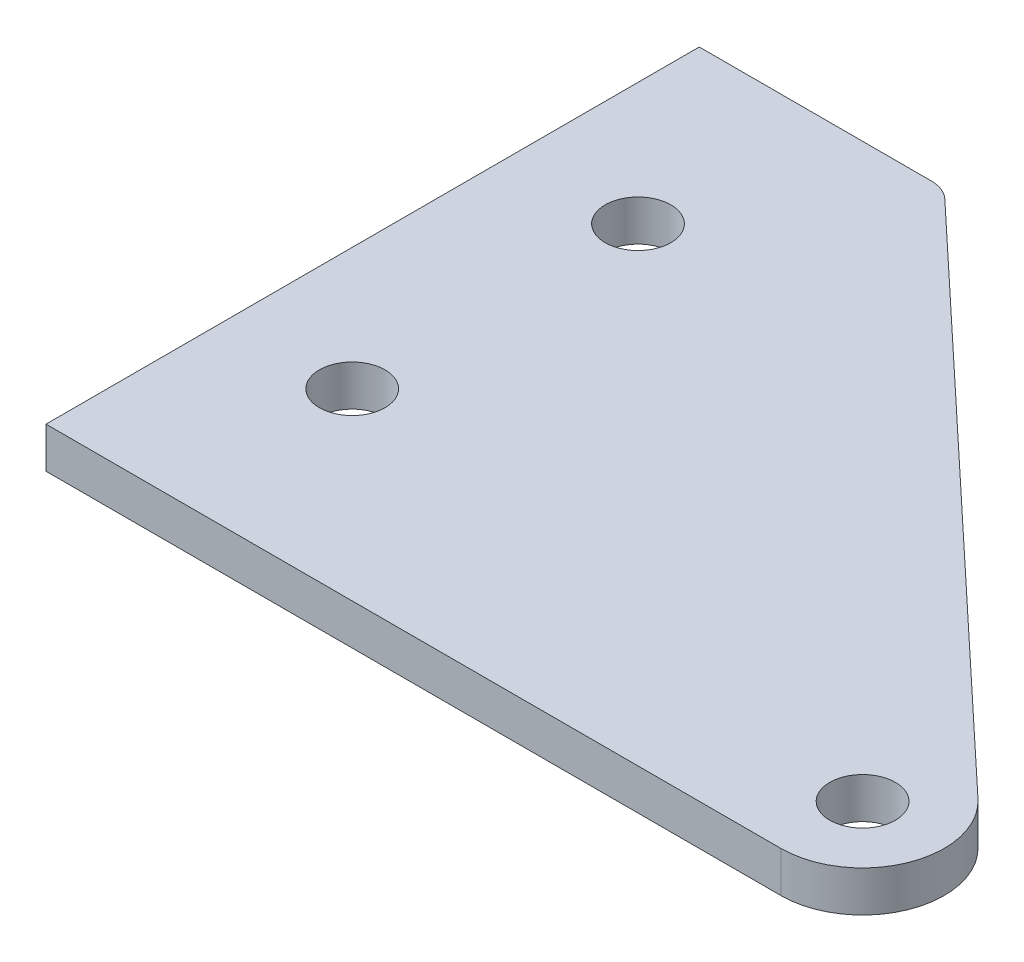
SolidWorks part; units mm, degrees
material "6061-T6 (SS)"
ref_plane "Front" through (0, 0, 0) normal (0, 0, 1) x (1, 0, 0)
ref_plane "Top" through (0, 0, 0) normal (0, 1, 0) x (1, 0, 0)
ref_plane "Right" through (0, 0, 0) normal (1, 0, 0) x (0, 0, -1)
sketch "Sketch1" plane through (0, 0, 0) normal (0, 1, 0) x (1, 0, 0)
  line L0 (0, 0) -> (0, 50.8)
  line L1 (0, 50.8) -> (19.05, 50.8)
  line L2 (0, 0) -> (57.15, 0)
  line L3 (19.05, 50.8) -> (61.4946, 10.9811)
  arc A0 (61.4946, 10.9811) -> (57.15, 0) centre (57.15, 6.35) cw
  dimension "D1" = 50.8
  dimension "D2" = 57.15
  dimension "D3" = 6.35
  dimension "D4" = 19.05
extrude "Boss-Extrude1" add sketch "Sketch1" along normal blind 3.175
hole_wizard "1/4-20 Tapped Hole1" positions "Sketch4" profile "Sketch3" tap size "1/4-20" standard "ANSI Inch" end condition through all
sketch "Sketch4" plane through (0, 0, 0) normal (0, -1, 0) x (-1, 0, 0)
  point P0 (-57.15, 6.35)
sketch "Sketch3" plane through (57.15, 0, -6.35) normal (1, 0, 0) x (0, 0, -1)
  line L0 (0, 0) -> (0, 3.175)
  line L1 (0, 3.175) -> (2.5527, 3.175)
  line L2 (2.5527, 3.175) -> (2.5527, 0)
  line L5 (2.5527, 0) -> (0, 0)
  line L11 (0, -6.35) -> (0, 107.95) construction
  dimension "Thru Tap Drill Dia." = 5.1054
  dimension "Thru Tap Drill Depth" = 3.175
cosmetic thread "Hole Thread1" parameters "D2"=6.35
hole_wizard "1/4-20 Tapped Hole2" positions "Sketch7" profile "Sketch8" tap size "1/4-20" standard "ANSI Inch" end condition through all
sketch "Sketch7" plane through (0, 3.175, 0) normal (0, 1, 0) x (1, 0, 0)
  line L4 (0, 0) -> (57.15, 0) construction
  line L7 (9.525, 50.8) -> (9.525, 0)
  line L8 (19.05, 50.8) -> (0, 50.8) construction
  point P0 (9.525, 36.5125)
  point P2 (9.525, 14.2875)
  dimension "D1" = 22.225
  dimension "D2" = 14.2875
sketch "Sketch8" plane through (9.525, 3.175, -36.5125) normal (1, 0, 0) x (0, 0, 1)
  line L0 (0, 0) -> (0, 3.175)
  line L1 (0, 3.175) -> (2.5527, 3.175)
  line L2 (2.5527, 3.175) -> (2.5527, 0)
  line L5 (2.5527, 0) -> (0, 0)
  line L11 (0, -6.35) -> (0, 107.95) construction
  dimension "Thru Tap Drill Dia." = 5.1054
  dimension "Thru Tap Drill Depth" = 3.175
cosmetic thread "Hole Thread2" parameters "D2"=6.35
cosmetic thread "Hole Thread3" parameters "D2"=6.35
fillet "Fillet1" radius 2.54 1 edges at (19.05, 1.5875, -50.8)
